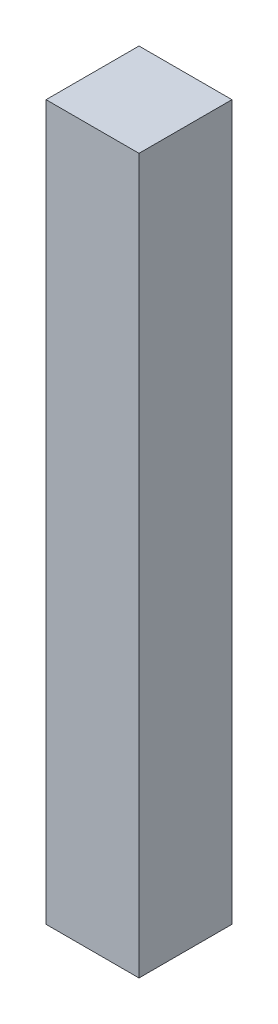
SolidWorks part; units mm, degrees
material "AISI 1020"
ref_plane "Front Plane" through (0, 0, 0) normal (0, 0, 1) x (1, 0, 0)
ref_plane "Top Plane" through (0, 0, 0) normal (0, 1, 0) x (1, 0, 0)
ref_plane "Right Plane" through (0, 0, 0) normal (1, 0, 0) x (0, 0, -1)
sketch "Sketch1" plane through (0, 0, 0) normal (0, 1, 0) x (1, 0, 0)
  line L1 (-19, -19) -> (19, -19)
  line L2 (-19, -19) -> (-19, 19)
  line L3 (-19, 19) -> (19, 19)
  line L4 (19, -19) -> (19, 19)
  line L5 (-19, -19) -> (19, 19) construction
  line L6 (-19, 19) -> (19, -19) construction
  point P0 (0, 0)
  dimension "D1" = 38
extrude "Boss-Extrude1" add sketch "Sketch1" along normal blind 146 and the other way blind 146
